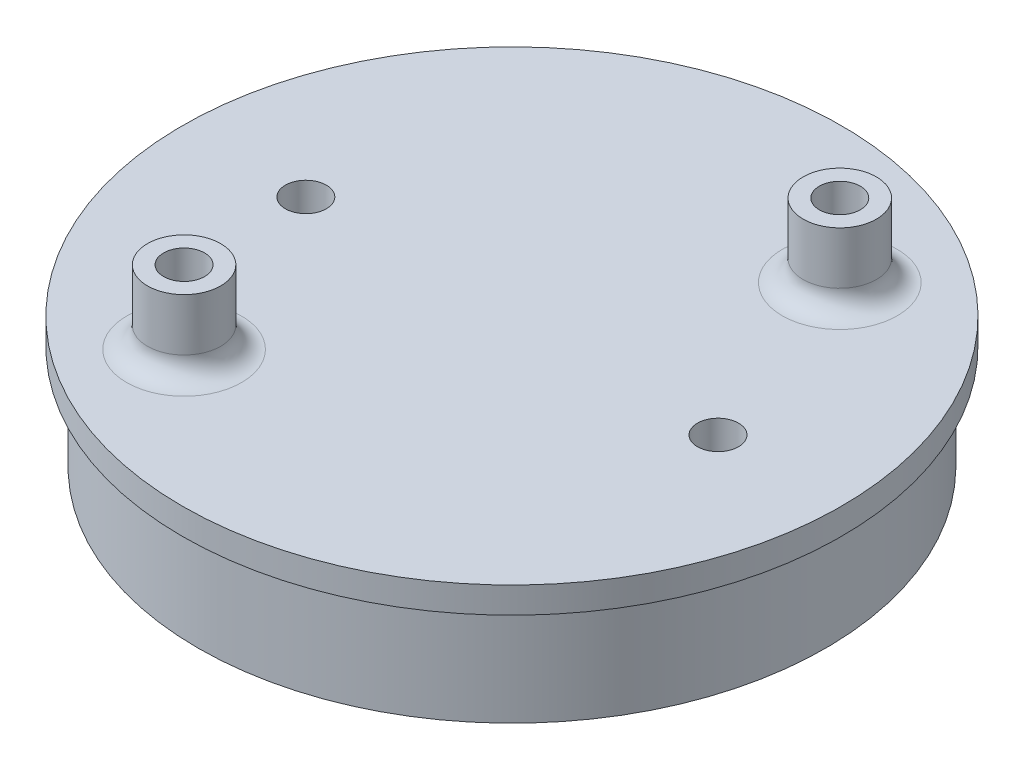
SolidWorks part; units mm, degrees
ref_plane "Front Plane" through (0, 0, 0) normal (0, 0, 1) x (1, 0, 0)
ref_plane "Top Plane" through (0, 0, 0) normal (0, 1, 0) x (1, 0, 0)
ref_plane "Right Plane" through (0, 0, 0) normal (1, 0, 0) x (0, 0, -1)
sketch "Sketch1" plane through (0, 0, 0) normal (0, 1, 0) x (1, 0, 0)
  circle A0 centre (0, 0) radius 38.1
  circle A1 centre (0, 0) radius 40.005
  dimension "D1" = 76.2
  dimension "D2" = 80.01
extrude "Boss-Extrude1" add sketch "Sketch1" along normal blind 3.175 contours A0 | A1 A0 | A0 | A1 region at (0, 0, 0) region at (-38.8735, 0, 0)
extrude "Boss-Extrude2" add sketch "Sketch1<3>" against normal blind 12.7 contours A0 region at (0, 0, 0)
sketch "Sketch1<3>" plane through (0, 0, 0) normal (0, 1, 0) x (1, 0, 0) same geometry as "Sketch1"
sketch "Sketch3" plane through (0, 3.175, 0) normal (0, 1, 0) x (1, 0, 0)
  line L0 (0, 40.005) -> (0, -40.005) construction
  circle A1 centre (-25.015, 0) radius 2.4892
  circle A2 centre (25.015, 0) radius 2.4892
  point P7 (0, 0)
  dimension "D1" = 4.9784
  dimension "D2" = 25.015
extrude "Cut-Extrude1" cut sketch "Sketch3" against normal through all both and the other way through all
sketch "Sketch4" plane through (0, 3.175, 0) normal (0, 1, 0) x (1, 0, 0)
  line L0 (-16.3899, -23.4073) -> (16.3899, 23.4073) construction
  line L1 (0, 0) -> (0, 40.005) construction
  line L2 (0, 0) -> (5.8048, -4.0646) construction
  circle A0 centre (16.3899, 23.4073) radius 4.445
  circle A1 centre (16.3899, 23.4073) radius 2.4892
  circle A2 centre (0, 0) radius 40.005 construction
  circle A3 centre (-16.3899, -23.4073) radius 4.445
  circle A4 centre (-16.3899, -23.4073) radius 2.4892
  point P5 (0, 0)
  dimension "D2" = 4.9784
  dimension "D3" = 8.89
  dimension "D1" = 57.15
  dimension "D4" = 35
extrude "Cut-Extrude2" cut sketch "Sketch4" against normal through all both and the other way through all contours A4 | A1 region at (16.3899, 3.175, -23.4073) region at (-16.3899, 3.175, 23.4073)
extrude "Boss-Extrude3" add sketch "Sketch4<3>" along normal blind 8.89
sketch "Sketch4<3>" plane through (0, 3.175, 0) normal (0, 1, 0) x (1, 0, 0) same geometry as "Sketch4"
fillet "Fillet1" radius 2.54 2 edges at (16.3899, 3.175, -18.9623) (-16.3899, 3.175, 18.9623)
